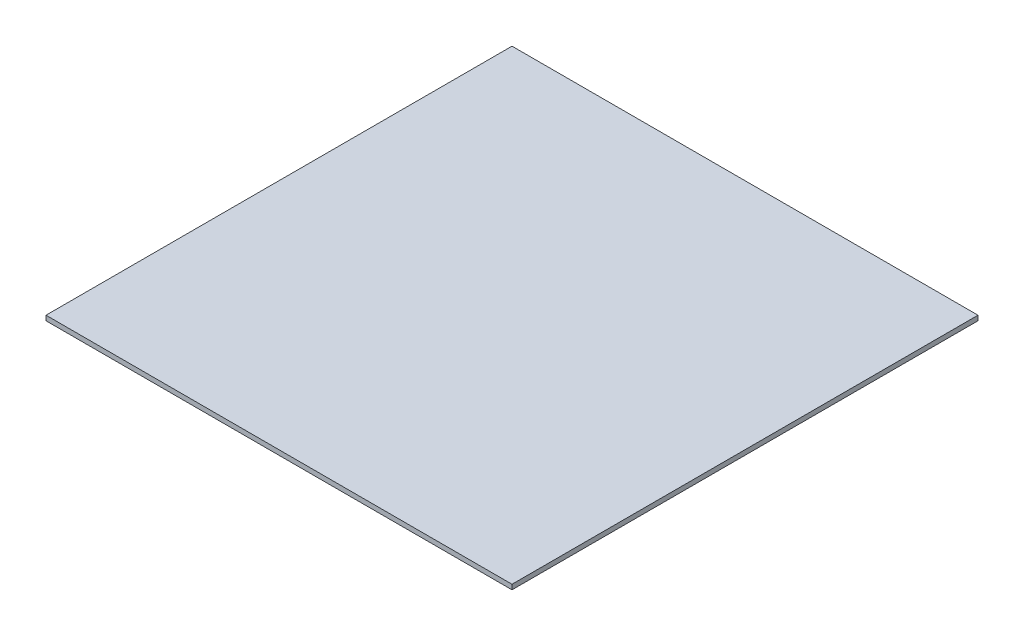
SolidWorks part; units mm, degrees
ref_plane "Front Plane" through (0, 0, 0) normal (0, 0, 1) x (1, 0, 0)
ref_plane "Top Plane" through (0, 0, 0) normal (0, 1, 0) x (1, 0, 0)
ref_plane "Right Plane" through (0, 0, 0) normal (1, 0, 0) x (0, 0, -1)
sketch "Sketch1" plane through (0, 0, 0) normal (0, 1, 0) x (1, 0, 0)
  line L1 (0, 0) -> (609.6, 0)
  line L2 (0, 0) -> (0, 609.6)
  line L3 (0, 609.6) -> (609.6, 609.6)
  line L4 (609.6, 0) -> (609.6, 609.6)
  dimension "D1" = 609.6
  dimension "D2" = 609.6
extrude "Boss-Extrude1" add sketch "Sketch1" along normal blind 6.35
